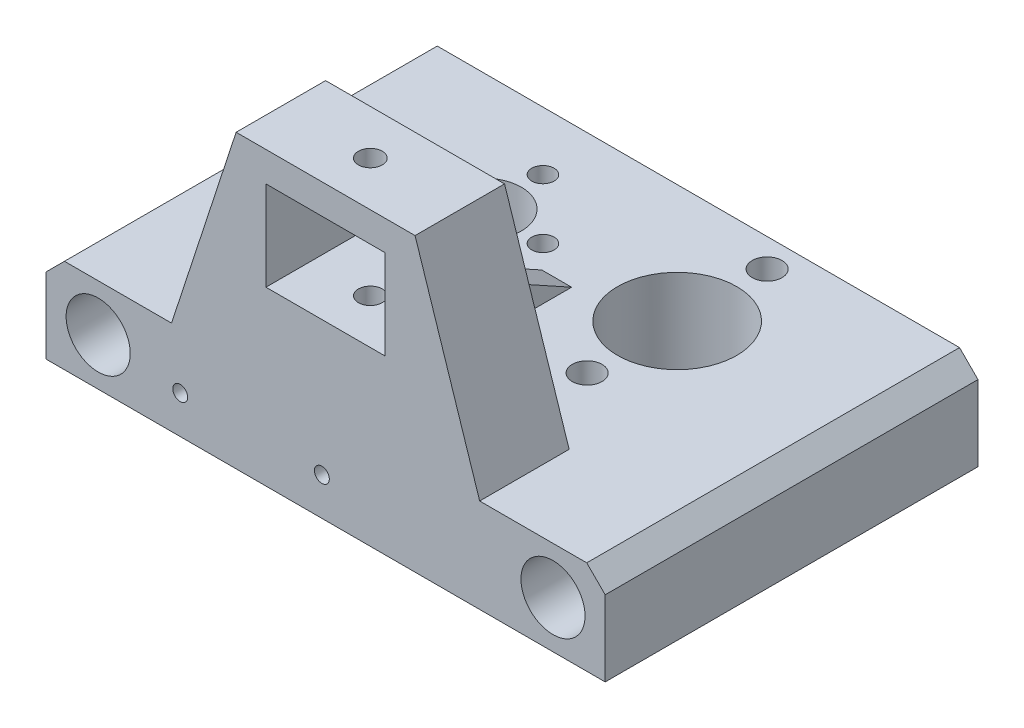
SolidWorks part; units mm, degrees
ref_plane "Front Plane" through (0, 0, 0) normal (0, 0, 1) x (1, 0, 0)
ref_plane "Top Plane" through (0, 0, 0) normal (0, 1, 0) x (1, 0, 0)
ref_plane "Right Plane" through (0, 0, 0) normal (1, 0, 0) x (0, 0, -1)
sketch "Sketch1" plane through (0, 0, 0) normal (0, 1, 0) x (1, 0, 0)
  line L0 (0, 34.15) -> (75, 34.15) construction
  line L1 (0, 0) -> (75, 0)
  line L2 (0, 0) -> (0, 50)
  line L3 (0, 50) -> (75, 50)
  line L4 (75, 0) -> (75, 50)
  line L5 (37.5, 50) -> (37.5, 0) construction
  line L6 (37.5, 34.15) -> (24.5, 34.15) construction
  line L7 (37.5, 34.15) -> (50.5, 34.15) construction
  circle A0 centre (24.5, 34.15) radius 5.1
  circle A1 centre (50.5, 34.15) radius 8
  point P15 (37.5, 34.15)
  dimension "D2" = 10.2
  dimension "D6" = 16
  dimension "D1" = 26
  dimension "D3" = 75
  dimension "D4" = 50
  dimension "D5" = 15.85
extrude "Boss-Extrude1" add sketch "Sketch1" along normal blind 0.1
sketch "Sketch2" plane through (0, 0.1, 0) normal (0, 1, 0) x (1, 0, 0)
  line L4 (0, 50) -> (12.5, 50)
  line L5 (0, 50) -> (0, 10)
  line L6 (0, 10) -> (12.5, 10)
  line L7 (12.5, 50) -> (12.5, 10)
  line L8 (75, 50) -> (62.5, 50)
  line L9 (75, 50) -> (75, 10)
  line L10 (75, 10) -> (62.5, 10)
  line L11 (62.5, 50) -> (62.5, 10)
  dimension "D1" = 40
  dimension "D3" = 12.5
extrude "Boss-Extrude2" add sketch "Sketch2" along normal blind 12.5
sketch "Sketch4" plane through (0, 0.1, 0) normal (0, 1, 0) x (1, 0, 0)
  line L0 (37.5, 0) -> (37.5, 50) construction
  line L1 (0, 0) -> (75, 0) construction
  line L2 (62.5, 50) -> (12.5, 50) construction
  line L4 (45.5, 0) -> (49.5, 0)
  line L5 (45.5, 0) -> (45.5, 12)
  line L6 (45.5, 12) -> (49.5, 12)
  line L7 (49.5, 0) -> (49.5, 12)
  line L8 (25.5, 0) -> (29.5, 0)
  line L9 (25.5, 0) -> (25.5, 12)
  line L10 (25.5, 12) -> (29.5, 12)
  line L11 (29.5, 0) -> (29.5, 12)
  dimension "D1" = 4
  dimension "D3" = 8
  dimension "D4" = 8
  dimension "D5" = 12
extrude "Boss-Extrude3" add sketch "Sketch4" along normal blind 35
sketch "Sketch5" plane through (0, 0, -12) normal (0, 0, -1) x (-1, 0, 0)
  line L0 (-49.5, 0.1) -> (-45.5, 0.1) construction
  line L1 (-49.5, 35.1) -> (-25.5, 35.1)
  line L2 (-49.5, 35.1) -> (-49.5, 39.1)
  line L3 (-49.5, 39.1) -> (-25.5, 39.1)
  line L4 (-25.5, 35.1) -> (-25.5, 39.1)
extrude "Boss-Extrude4" add sketch "Sketch5" against normal up to surface (12 mm away) up to face at (37.5, 11.75, 0)
sketch "Sketch7" plane through (0, 0.1, 0) normal (0, 1, 0) x (1, 0, 0)
  line L0 (50.5, 26.15) -> (50.5, 42.15) construction
  line L1 (24.5, 39.25) -> (24.5, 29.05) construction
  line L2 (29.6, 34.15) -> (19.4, 34.15) construction
  circle A1 centre (50.5, 22.08) radius 2
  circle A2 centre (50.5, 46.215) radius 2
  circle A3 centre (50.5, 34.15) radius 8 construction
  circle A4 centre (24.5, 34.15) radius 5.1 construction
  circle A6 centre (24.5, 42.15) radius 1.5
  circle A7 centre (16.5, 34.15) radius 1.5
  circle A8 centre (32.5, 34.15) radius 1.5
  circle A9 centre (24.5, 26.15) radius 1.5
  point P10 (50.5, 34.15)
  point P20 (24.5, 34.15)
  dimension "D3" = 4
  dimension "D6" = 3
  dimension "D1" = 12.065
  dimension "D2" = 12.07
  dimension "D4" = 8
  dimension "D5" = 8
extrude "Cut-Extrude4" cut sketch "Sketch7" against normal through all
sketch "Sketch8" plane through (0, 0.1, 0) normal (0, 1, 0) x (1, 0, 0)
  line L1 (45.5, 0) -> (29.5, 0)
  line L2 (45.5, 0) -> (45.5, 12)
  line L3 (45.5, 12) -> (29.5, 12)
  line L4 (29.5, 0) -> (29.5, 12)
extrude "Boss-Extrude5" add sketch "Sketch8" along normal blind 23
sketch "Sketch9" plane through (0, 0, 0) normal (0, 0, 1) x (1, 0, 0)
  line L0 (49.5, 39.1) -> (62.25, 0.1)
  line L1 (49.5, 0.1) -> (75, 0.1) construction
  line L2 (62.25, 0.1) -> (49.5, 0.1)
  line L3 (49.5, 0.1) -> (49.5, 39.1)
  line L4 (37.5, 23.1) -> (37.5, 35.1) construction
  line L5 (29.5, 23.1) -> (45.5, 23.1) construction
  line L6 (29.5, 35.1) -> (45.5, 35.1) construction
  line L7 (12.75, 0.1) -> (25.5, 0.1)
  line L8 (25.5, 39.1) -> (12.75, 0.1)
  line L9 (25.5, 0.1) -> (25.5, 39.1)
extrude "Boss-Extrude6" add sketch "Sketch9" against normal up to surface (12 mm away) up to face at (37.5, 19.6, -12)
sketch "Sketch6" plane through (0, 39.1, 0) normal (0, 1, 0) x (1, 0, 0)
  line L0 (49.5, 6) -> (25.5, 6) construction
  line L3 (37.5, 0) -> (37.5, 12) construction
  line L4 (49.5, 0) -> (25.5, 0) construction
  line L5 (25.5, 12) -> (49.5, 12) construction
  line L6 (25.5, 0) -> (25.5, 12) construction
  line L7 (49.5, 0) -> (49.5, 12) construction
  circle A0 centre (37.5, 6) radius 1.6
  dimension "D1" = 3.2
extrude "Cut-Extrude2" cut sketch "Sketch6" against normal blind 25
sketch "Sketch10" plane through (0, 0.1, 0) normal (0, 1, 0) x (1, 0, 0)
  line L0 (62.25, 12) -> (12.75, 12) construction
  line L1 (39.5, 12) -> (35.5, 12)
  line L2 (39.5, 12) -> (39.5, 50)
  line L3 (39.5, 50) -> (35.5, 50)
  line L4 (35.5, 12) -> (35.5, 50)
  line L5 (37.5, 12) -> (37.5, 50) construction
  line L6 (62.5, 50) -> (12.5, 50) construction
  point P6 (37.5, 50)
  dimension "D1" = 4
extrude "Boss-Extrude7" add sketch "Sketch10" along normal blind 2
sketch "Sketch11" plane through (39.5, 0, 0) normal (1, 0, 0) x (0, 0, -1)
  line L0 (50, 2.1) -> (12, 2.1)
  line L1 (12, 2.1) -> (12, 23.1)
  line L2 (12, 23.1) -> (50, 2.1)
extrude "Boss-Extrude8" add sketch "Sketch11" against normal up to surface (4 mm away) up to face at (35.5, 1.1, -31)
sketch "Sketch12" plane through (0, 0.1, 0) normal (0, 1, 0) x (1, 0, 0)
  line L1 (39.5, 12) -> (44.5, 12)
  line L2 (39.5, 12) -> (39.5, 16.6)
  line L3 (39.5, 16.6) -> (44.5, 16.6)
  line L4 (44.5, 12) -> (44.5, 16.6)
  line L5 (35.5, 12) -> (30.5, 12)
  line L6 (35.5, 12) -> (35.5, 16.6)
  line L7 (35.5, 16.6) -> (30.5, 16.6)
  line L8 (30.5, 12) -> (30.5, 16.6)
  dimension "D1" = 5
  dimension "D2" = 4.6
revolve "Revolve1" add sketch "Sketch12" angle 90 about L1 region at (33, 0.1, -14.3)
sketch "Sketch14" plane through (0, 0.1, 0) normal (0, 1, 0) x (1, 0, 0)
  line L1 (75, 0) -> (0, 0)
  line L2 (75, 0) -> (75, 10)
  line L3 (75, 10) -> (0, 10)
  line L4 (0, 0) -> (0, 10)
  line L5 (62.5, 10) -> (12.5, 10)
  line L6 (62.5, 10) -> (62.5, 50)
  line L7 (62.5, 50) -> (12.5, 50)
  line L8 (12.5, 10) -> (12.5, 50)
  circle A0 centre (50.5, 22.08) radius 2
  circle A1 centre (50.5, 22.08) radius 2 construction
  circle A2 centre (50.5, 34.15) radius 8
  circle A3 centre (50.5, 46.215) radius 2
  circle A4 centre (32.5, 34.15) radius 1.5
  circle A5 centre (24.5, 34.15) radius 5.1
  circle A6 centre (16.5, 34.15) radius 1.5
  circle A7 centre (24.5, 26.15) radius 1.5
  circle A8 centre (24.5, 42.15) radius 1.5
  circle A9 centre (24.5, 42.15) radius 1.5 construction
  circle A10 centre (24.5, 34.15) radius 5.1 construction
  circle A11 centre (50.5, 46.215) radius 2 construction
  circle A12 centre (50.5, 34.15) radius 8 construction
  circle M8 centre (50.5, 22.08) radius 2
  circle M9 centre (50.5, 46.215) radius 2
  circle M10 centre (50.5, 34.15) radius 8
  line M11 (39.5, 50) -> (39.5, 16.6)
  line M12 (39.5, 16.6) -> (44.5, 16.6)
  line M13 (44.5, 16.6) -> (44.5, 12)
  line M14 (44.5, 12) -> (62.25, 12)
  line M15 (62.25, 12) -> (62.25, 0)
  line M16 (62.25, 0) -> (75, 0)
  line M17 (75, 0) -> (75, 10)
  line M18 (75, 10) -> (62.5, 10)
  line M19 (62.5, 10) -> (62.5, 50)
  line M20 (62.5, 50) -> (39.5, 50)
extrude "Boss-Extrude9" add sketch "Sketch14" along normal up to surface (12.5 mm away) contours L3 M19 M20 M11 M12 M13 M14 M15 M9 M10 M8 | L3 M18 M15 M16 M17 | L8 L3 L7 A8 A7 A6 A5 A4 M15 M14 M13 M12 M11 | L4 L1 L3 M15 region at (68.625, 0.1, -5) region at (31.125, 0.1, -5) region at (62.2961, 0.1, -11) region at (27.6031, 0.1, -28.3803) up to face at (68.75, 12.6, -30)
sketch "Sketch3" plane through (0, 0, -50) normal (0, 0, -1) x (-1, 0, 0)
  line L0 (-37.5, 0) -> (-37.5, 50000) construction
  line L1 (-75, 0) -> (0, 0) construction
  line L3 (-72.5251, 12.6) -> (-75, 12.6)
  line L4 (-75, 12.6) -> (0, 12.6) construction
  line L5 (-75, 12.6) -> (-75, 10.1251)
  line L6 (-75, 12.6) -> (-75, 0) construction
  line L7 (-75, 10.1251) -> (-72.5251, 12.6)
  line L12 (-37.5, 12.6) -> (-37.5, 0) construction
  line L13 (-61, 6.3) -> (-75, 6.3) construction
  line L14 (-14, 6.3) -> (0, 6.3) construction
  line L15 (-37.5, 12.6) -> (-37.5, 0) construction
  line L19 (0, 10.1251) -> (-2.4749, 12.6)
  line L20 (0, 12.6) -> (0, 10.1251)
  line L21 (-2.4749, 12.6) -> (0, 12.6)
  line L22 (-75, 12.6) -> (-75, 0) construction
  circle A0 centre (-68, 6.3) radius 4.3
  circle A1 centre (-7, 6.3) radius 4.3
  point P4 (-37.5, 0)
  dimension "D1" = 8.6
  dimension "D2" = 3.5
  dimension "D3" = 14
extrude "Cut-Extrude1" cut sketch "Sketch3" against normal through all
sketch "Sketch15" plane through (0, 0, 0) normal (0, 0, 1) x (1, 0, 0)
  line L0 (0, 5.0626) -> (75, 5.0626) construction
  line L1 (0, 10.1251) -> (0, 0) construction
  line L2 (75, 10.1251) -> (75, 0) construction
  line L3 (37.5, 39.1) -> (37.5, 0) construction
  line L4 (49.5, 39.1) -> (25.5, 39.1) construction
  line L5 (0, 0) -> (75, 0) construction
  circle A0 centre (18, 5.0626) radius 1
  circle A1 centre (37, 5.0626) radius 1
  dimension "D3" = 2
  dimension "D1" = 19
  dimension "D2" = 0.5
extrude "Cut-Extrude5" cut sketch "Sketch15" against normal blind 8
equation "\"8mm hole\" = 8.6mm"
equation "\"22mm hole\"= 23mm"
equation "\"15mm hole\"= 16mm"
equation "\"D6@Sketch1\"= \"15mm hole\""
equation "\"D1@Sketch3\"= \"8mm hole\""
